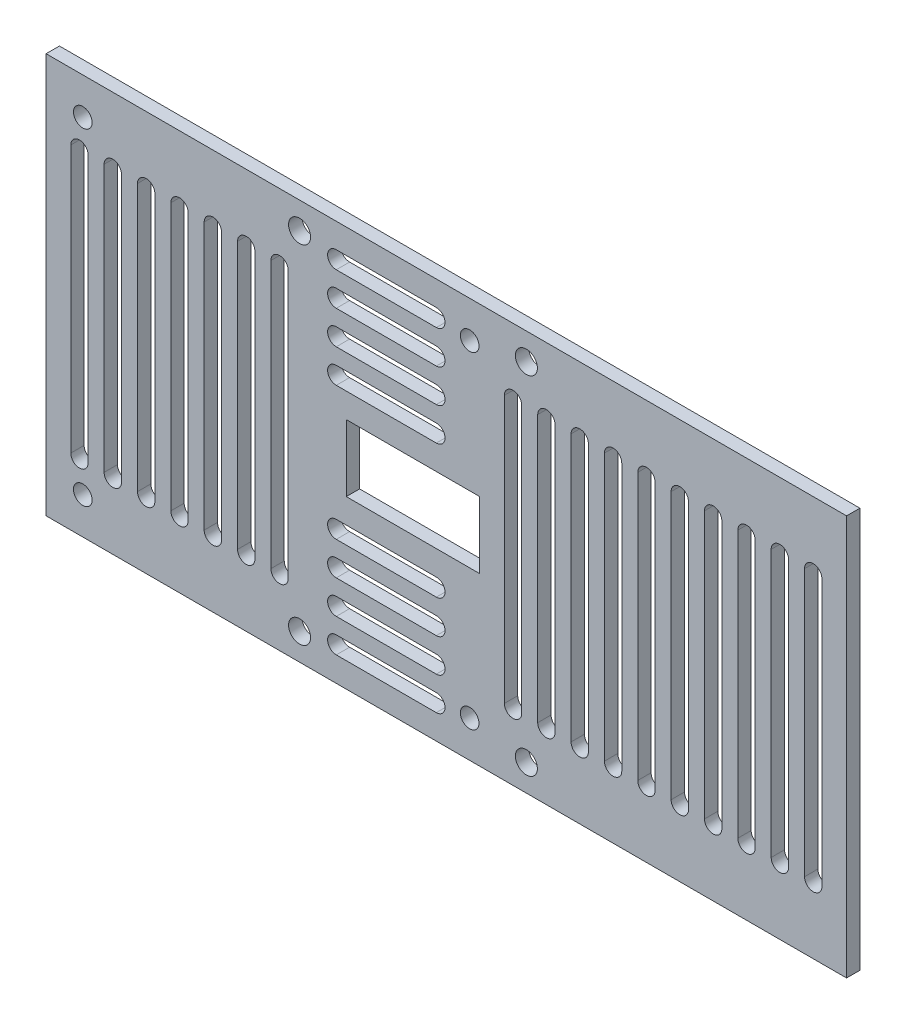
SolidWorks part; units mm, degrees
ref_plane "前视基准面" through (0, 0, 0) normal (0, 0, 1) x (1, 0, 0)
ref_plane "上视基准面" through (0, 0, 0) normal (0, 1, 0) x (1, 0, 0)
ref_plane "右视基准面" through (0, 0, 0) normal (1, 0, 0) x (0, 0, -1)
sketch "草图4" plane through (0, 0, 0) normal (0, 0, 1) x (1, 0, 0)
  line L0 (0, 0) -> (0, -30) construction
  line L1 (-39, 30) -> (39, 30)
  line L2 (-55, 14) -> (-55, -14)
  line L3 (-39, -30) -> (39, -30)
  line L5 (-55, 30) -> (55, -30) construction
  line L6 (-55, -30) -> (55, 30) construction
  line L7 (-1.4897, 0) -> (53.5103, 0) construction
  line L9 (-10, 5) -> (10, 5)
  line L10 (-10, 5) -> (-10, -5)
  line L11 (-10, -5) -> (10, -5)
  line L12 (10, 5) -> (10, -5)
  line L13 (-10, 5) -> (10, -5) construction
  line L14 (-10, -5) -> (10, 5) construction
  line L24 (-39, 30) -> (-55, 30)
  line L25 (-55, 30) -> (-55, 14)
  line L26 (-55, -14) -> (-55, -30)
  line L27 (-55, -30) -> (-39, -30)
  line L28 (39, 30) -> (55, 30)
  line L29 (55, 30) -> (65, 30)
  line L30 (65, 30) -> (65, -30)
  line L31 (65, -30) -> (39, -30)
  circle A0 centre (-49.5, 24.5) radius 1.4
  circle A1 centre (8.5, 24.5) radius 1.4
  circle A2 centre (17, 26) radius 1.65
  circle A3 centre (-17, 26) radius 1.65
  circle A4 centre (-17, -26) radius 1.65
  circle A5 centre (17, -26) radius 1.65
  circle A6 centre (8.5, -24.5) radius 1.4
  circle A7 centre (-49.5, -24.5) radius 1.4
  circle A8 centre (8.5, 24.5) radius 2.5 construction
  circle A9 centre (17, 26) radius 2.5 construction
  point P0 (0, 0)
  point P28 (0, 0)
  dimension "D3" = 2.8
  dimension "D4" = 2.8
  dimension "D9" = 3.3
  dimension "D10" = 3.3
  dimension "D15" = 5
  dimension "D16" = 5
  dimension "D17" = 10
  dimension "D1" = 110
  dimension "D2" = 60
  dimension "D5" = 5.5
  dimension "D6" = 58
  dimension "D7" = 5.5
  dimension "D8" = 5.5
  dimension "D11" = 26
  dimension "D12" = 26
  dimension "D13" = 34
  dimension "D14" = 17
  dimension "D18" = 20
  dimension "D19" = 10
extrude "凸台-拉伸2" add sketch "草图4" along normal blind 2
sketch "草图5" plane through (0, 0, 2) normal (0, 0, 1) x (1, 0, 0)
  line L0 (-50, 20) -> (-50, -20) construction
  line L1 (-48.7, 20) -> (-48.7, -20)
  line L2 (-51.3, 20) -> (-51.3, -20)
  line L3 (-55, -30) -> (65, -30) construction
  line L5 (-55, 30) -> (-55, -30) construction
  line L6 (-11.5, 25) -> (3.5, 25) construction
  line L7 (-11.5, 26.3) -> (3.5, 26.3)
  line L8 (-11.5, 23.7) -> (3.5, 23.7)
  line L9 (65, 30) -> (-55, 30) construction
  line L10 (-45, 20) -> (-45, -20) construction
  line L11 (-43.7, 20) -> (-43.7, -20)
  line L12 (-46.3, 20) -> (-46.3, -20)
  line L13 (-40, 20) -> (-40, -20) construction
  line L14 (-38.7, 20) -> (-38.7, -20)
  line L15 (-41.3, 20) -> (-41.3, -20)
  line L16 (-35, 20) -> (-35, -20) construction
  line L17 (-33.7, 20) -> (-33.7, -20)
  line L18 (-36.3, 20) -> (-36.3, -20)
  line L19 (-30, 20) -> (-30, -20) construction
  line L20 (-28.7, 20) -> (-28.7, -20)
  line L21 (-31.3, 20) -> (-31.3, -20)
  line L22 (-25, 20) -> (-25, -20) construction
  line L23 (-23.7, 20) -> (-23.7, -20)
  line L24 (-26.3, 20) -> (-26.3, -20)
  line L25 (-20, 20) -> (-20, -20) construction
  line L26 (-18.7, 20) -> (-18.7, -20)
  line L27 (-21.3, 20) -> (-21.3, -20)
  line L40 (-11.5, 20) -> (3.5, 20) construction
  line L46 (15, 20) -> (15, -20) construction
  line L47 (16.3, 20) -> (16.3, -20)
  line L48 (13.7, 20) -> (13.7, -20)
  line L49 (20, 20) -> (20, -20) construction
  line L50 (21.3, 20) -> (21.3, -20)
  line L51 (18.7, 20) -> (18.7, -20)
  line L52 (25, 20) -> (25, -20) construction
  line L53 (26.3, 20) -> (26.3, -20)
  line L54 (23.7, 20) -> (23.7, -20)
  line L55 (30, 20) -> (30, -20) construction
  line L56 (31.3, 20) -> (31.3, -20)
  line L57 (28.7, 20) -> (28.7, -20)
  line L58 (35, 20) -> (35, -20) construction
  line L59 (36.3, 20) -> (36.3, -20)
  line L60 (33.7, 20) -> (33.7, -20)
  line L61 (40, 20) -> (40, -20) construction
  line L62 (41.3, 20) -> (41.3, -20)
  line L63 (38.7, 20) -> (38.7, -20)
  line L64 (45, 20) -> (45, -20) construction
  line L65 (46.3, 20) -> (46.3, -20)
  line L66 (43.7, 20) -> (43.7, -20)
  line L67 (50, 20) -> (50, -20) construction
  line L68 (51.3, 20) -> (51.3, -20)
  line L69 (48.7, 20) -> (48.7, -20)
  line L70 (55, 20) -> (55, -20) construction
  line L71 (56.3, 20) -> (56.3, -20)
  line L72 (53.7, 20) -> (53.7, -20)
  line L73 (60, 20) -> (60, -20) construction
  line L74 (61.3, 20) -> (61.3, -20)
  line L75 (58.7, 20) -> (58.7, -20)
  line L87 (-11.5, 21.3) -> (3.5, 21.3)
  line L88 (-11.5, 18.7) -> (3.5, 18.7)
  line L89 (-11.5, 15) -> (3.5, 15) construction
  line L90 (-11.5, 16.3) -> (3.5, 16.3)
  line L91 (-11.5, 13.7) -> (3.5, 13.7)
  line L92 (-11.5, 10) -> (3.5, 10) construction
  line L93 (-11.5, 11.3) -> (3.5, 11.3)
  line L94 (-11.5, 8.7) -> (3.5, 8.7)
  line L104 (-11.5, -10) -> (3.5, -10) construction
  line L105 (-11.5, -8.7) -> (3.5, -8.7)
  line L106 (-11.5, -11.3) -> (3.5, -11.3)
  line L107 (-11.5, -15) -> (3.5, -15) construction
  line L108 (-11.5, -13.7) -> (3.5, -13.7)
  line L109 (-11.5, -16.3) -> (3.5, -16.3)
  line L110 (-11.5, -20) -> (3.5, -20) construction
  line L111 (-11.5, -18.7) -> (3.5, -18.7)
  line L112 (-11.5, -21.3) -> (3.5, -21.3)
  line L113 (-11.5, -25) -> (3.5, -25) construction
  line L114 (-11.5, -23.7) -> (3.5, -23.7)
  line L115 (-11.5, -26.3) -> (3.5, -26.3)
  line L125 (-10, 20) -> (-10, -20) construction
  line L126 (-8.7, 20) -> (-8.7, -20)
  line L127 (-11.3, 20) -> (-11.3, -20)
  line L128 (-5, 20) -> (-5, -20) construction
  line L129 (-3.7, 20) -> (-3.7, -20)
  line L130 (-6.3, 20) -> (-6.3, -20)
  line L131 (0, 20) -> (0, -20) construction
  line L132 (1.3, 20) -> (1.3, -20)
  line L133 (-1.3, 20) -> (-1.3, -20)
  line L134 (5, 20) -> (5, -20) construction
  line L135 (6.3, 20) -> (6.3, -20)
  line L136 (3.7, 20) -> (3.7, -20)
  line L137 (-15, 20) -> (-15, -20) construction
  line L138 (-13.7, 20) -> (-13.7, -20)
  line L139 (-16.3, 20) -> (-16.3, -20)
  line L140 (-11.5, 0) -> (3.5, 0) construction
  line L141 (-11.5, 1.3) -> (3.5, 1.3)
  line L142 (-11.5, -1.3) -> (3.5, -1.3)
  line L143 (-11.5, -5) -> (3.5, -5) construction
  line L144 (-11.5, -3.7) -> (3.5, -3.7)
  line L145 (-11.5, -6.3) -> (3.5, -6.3)
  line L146 (10, 20) -> (10, -20) construction
  line L147 (11.3, 20) -> (11.3, -20)
  line L148 (8.7, 20) -> (8.7, -20)
  line L149 (-11.5, 5) -> (3.5, 5) construction
  line L150 (-11.5, 6.3) -> (3.5, 6.3)
  line L151 (-11.5, 3.7) -> (3.5, 3.7)
  line L152 (-10, 20) -> (-10, -20) construction
  line L153 (-8.7, 20) -> (-8.7, -20)
  line L154 (-11.3, 20) -> (-11.3, -20)
  line L155 (-5, 20) -> (-5, -20) construction
  line L156 (-3.7, 20) -> (-3.7, -20)
  line L157 (-6.3, 20) -> (-6.3, -20)
  line L158 (0, 20) -> (0, -20) construction
  line L159 (1.3, 20) -> (1.3, -20)
  line L160 (-1.3, 20) -> (-1.3, -20)
  line L161 (5, 20) -> (5, -20) construction
  line L162 (6.3, 20) -> (6.3, -20)
  line L163 (3.7, 20) -> (3.7, -20)
  line L164 (-15, 20) -> (-15, -20) construction
  line L165 (-13.7, 20) -> (-13.7, -20)
  line L166 (-16.3, 20) -> (-16.3, -20)
  line L167 (-11.5, 0) -> (3.5, 0) construction
  line L168 (-11.5, 1.3) -> (3.5, 1.3)
  line L169 (-11.5, -1.3) -> (3.5, -1.3)
  line L170 (-11.5, -5) -> (3.5, -5) construction
  line L171 (-11.5, -3.7) -> (3.5, -3.7)
  line L172 (-11.5, -6.3) -> (3.5, -6.3)
  line L173 (10, 20) -> (10, -20) construction
  line L174 (11.3, 20) -> (11.3, -20)
  line L175 (8.7, 20) -> (8.7, -20)
  line L176 (-11.5, 5) -> (3.5, 5) construction
  line L177 (-11.5, 6.3) -> (3.5, 6.3)
  line L178 (-11.5, 3.7) -> (3.5, 3.7)
  arc A0 (-48.7, 20) -> (-51.3, 20) centre (-50, 20) ccw
  arc A1 (-51.3, -20) -> (-48.7, -20) centre (-50, -20) ccw
  arc A2 (-11.5, 26.3) -> (-11.5, 23.7) centre (-11.5, 25) ccw
  arc A3 (3.5, 23.7) -> (3.5, 26.3) centre (3.5, 25) ccw
  arc A4 (-43.7, 20) -> (-46.3, 20) centre (-45, 20) ccw
  arc A5 (-46.3, -20) -> (-43.7, -20) centre (-45, -20) ccw
  arc A6 (-38.7, 20) -> (-41.3, 20) centre (-40, 20) ccw
  arc A7 (-41.3, -20) -> (-38.7, -20) centre (-40, -20) ccw
  arc A8 (-33.7, 20) -> (-36.3, 20) centre (-35, 20) ccw
  arc A9 (-36.3, -20) -> (-33.7, -20) centre (-35, -20) ccw
  arc A10 (-28.7, 20) -> (-31.3, 20) centre (-30, 20) ccw
  arc A11 (-31.3, -20) -> (-28.7, -20) centre (-30, -20) ccw
  arc A12 (-23.7, 20) -> (-26.3, 20) centre (-25, 20) ccw
  arc A13 (-26.3, -20) -> (-23.7, -20) centre (-25, -20) ccw
  arc A14 (-18.7, 20) -> (-21.3, 20) centre (-20, 20) ccw
  arc A15 (-21.3, -20) -> (-18.7, -20) centre (-20, -20) ccw
  arc A28 (16.3, 20) -> (13.7, 20) centre (15, 20) ccw
  arc A29 (13.7, -20) -> (16.3, -20) centre (15, -20) ccw
  arc A30 (21.3, 20) -> (18.7, 20) centre (20, 20) ccw
  arc A31 (18.7, -20) -> (21.3, -20) centre (20, -20) ccw
  arc A32 (26.3, 20) -> (23.7, 20) centre (25, 20) ccw
  arc A33 (23.7, -20) -> (26.3, -20) centre (25, -20) ccw
  arc A34 (31.3, 20) -> (28.7, 20) centre (30, 20) ccw
  arc A35 (28.7, -20) -> (31.3, -20) centre (30, -20) ccw
  arc A36 (36.3, 20) -> (33.7, 20) centre (35, 20) ccw
  arc A37 (33.7, -20) -> (36.3, -20) centre (35, -20) ccw
  arc A38 (41.3, 20) -> (38.7, 20) centre (40, 20) ccw
  arc A39 (38.7, -20) -> (41.3, -20) centre (40, -20) ccw
  arc A40 (46.3, 20) -> (43.7, 20) centre (45, 20) ccw
  arc A41 (43.7, -20) -> (46.3, -20) centre (45, -20) ccw
  arc A42 (51.3, 20) -> (48.7, 20) centre (50, 20) ccw
  arc A43 (48.7, -20) -> (51.3, -20) centre (50, -20) ccw
  arc A44 (56.3, 20) -> (53.7, 20) centre (55, 20) ccw
  arc A45 (53.7, -20) -> (56.3, -20) centre (55, -20) ccw
  arc A46 (61.3, 20) -> (58.7, 20) centre (60, 20) ccw
  arc A47 (58.7, -20) -> (61.3, -20) centre (60, -20) ccw
  arc A58 (-11.5, 21.3) -> (-11.5, 18.7) centre (-11.5, 20) ccw
  arc A59 (3.5, 18.7) -> (3.5, 21.3) centre (3.5, 20) ccw
  arc A60 (-11.5, 16.3) -> (-11.5, 13.7) centre (-11.5, 15) ccw
  arc A61 (3.5, 13.7) -> (3.5, 16.3) centre (3.5, 15) ccw
  arc A62 (-11.5, 11.3) -> (-11.5, 8.7) centre (-11.5, 10) ccw
  arc A63 (3.5, 8.7) -> (3.5, 11.3) centre (3.5, 10) ccw
  arc A70 (-11.5, -8.7) -> (-11.5, -11.3) centre (-11.5, -10) ccw
  arc A71 (3.5, -11.3) -> (3.5, -8.7) centre (3.5, -10) ccw
  arc A72 (-11.5, -13.7) -> (-11.5, -16.3) centre (-11.5, -15) ccw
  arc A73 (3.5, -16.3) -> (3.5, -13.7) centre (3.5, -15) ccw
  arc A74 (-11.5, -18.7) -> (-11.5, -21.3) centre (-11.5, -20) ccw
  arc A75 (3.5, -21.3) -> (3.5, -18.7) centre (3.5, -20) ccw
  arc A76 (-11.5, -23.7) -> (-11.5, -26.3) centre (-11.5, -25) ccw
  arc A77 (3.5, -26.3) -> (3.5, -23.7) centre (3.5, -25) ccw
  arc A104 (-8.7, 20) -> (-11.3, 20) centre (-10, 20) ccw
  arc A105 (-11.3, -20) -> (-8.7, -20) centre (-10, -20) ccw
  arc A106 (-3.7, 20) -> (-6.3, 20) centre (-5, 20) ccw
  arc A107 (-6.3, -20) -> (-3.7, -20) centre (-5, -20) ccw
  arc A108 (1.3, 20) -> (-1.3, 20) centre (0, 20) ccw
  arc A109 (-1.3, -20) -> (1.3, -20) centre (0, -20) ccw
  arc A110 (6.3, 20) -> (3.7, 20) centre (5, 20) ccw
  arc A111 (3.7, -20) -> (6.3, -20) centre (5, -20) ccw
  arc A112 (-13.7, 20) -> (-16.3, 20) centre (-15, 20) ccw
  arc A113 (-16.3, -20) -> (-13.7, -20) centre (-15, -20) ccw
  arc A114 (-11.5, 1.3) -> (-11.5, -1.3) centre (-11.5, 0) ccw
  arc A115 (3.5, -1.3) -> (3.5, 1.3) centre (3.5, 0) ccw
  arc A116 (-11.5, -3.7) -> (-11.5, -6.3) centre (-11.5, -5) ccw
  arc A117 (3.5, -6.3) -> (3.5, -3.7) centre (3.5, -5) ccw
  arc A118 (11.3, 20) -> (8.7, 20) centre (10, 20) ccw
  arc A119 (8.7, -20) -> (11.3, -20) centre (10, -20) ccw
  arc A120 (-11.5, 6.3) -> (-11.5, 3.7) centre (-11.5, 5) ccw
  arc A121 (3.5, 3.7) -> (3.5, 6.3) centre (3.5, 5) ccw
  point P2 (-50, 0)
  point P13 (-4, 25)
  point P24 (-45, 0)
  point P31 (-40, 0)
  point P38 (-35, 0)
  point P45 (-30, 0)
  point P52 (-25, 0)
  point P59 (-20, 0)
  point P66 (-10, 0)
  point P73 (-5, 0)
  point P80 (0, 0)
  point P87 (5, 0)
  point P95 (-4, 20)
  point P108 (15, 0)
  point P115 (20, 0)
  point P122 (25, 0)
  point P129 (30, 0)
  point P136 (35, 0)
  point P143 (40, 0)
  point P150 (45, 0)
  point P157 (50, 0)
  point P164 (55, 0)
  point P171 (60, 0)
  point P176 (-15, 0)
  point P184 (-4, 15)
  point P191 (-4, 10)
  point P198 (-4, 0)
  point P205 (-4, -5)
  point P212 (10, 0)
  point P219 (-4, -10)
  point P226 (-4, -15)
  point P233 (-4, -20)
  point P240 (-4, -25)
  point P246 (-4, 5)
  point P253 (-10, 0)
  point P260 (-5, 0)
  point P267 (0, 0)
  point P274 (5, 0)
  point P281 (-15, 0)
  point P288 (-4, 0)
  point P295 (-4, -5)
  point P302 (10, 0)
  point P309 (-4, 5)
  point P316 (-10, 0)
  point P323 (-5, 0)
  point P330 (0, 0)
  point P337 (5, 0)
  point P344 (-15, 0)
  point P351 (-4, 0)
  point P358 (-4, -5)
  point P365 (10, 0)
  point P372 (-4, 5)
  dimension "D1" = 1.3
  dimension "D5" = 1.3
  dimension "D2" = 40
  dimension "D3" = 30
  dimension "D4" = 5
  dimension "D6" = 15
  dimension "D7" = 51
  dimension "D8" = 5
  dimension "D9" = 23
  dimension "D10" = 11
extrude "切除-拉伸1" cut sketch "草图5" against normal through all
